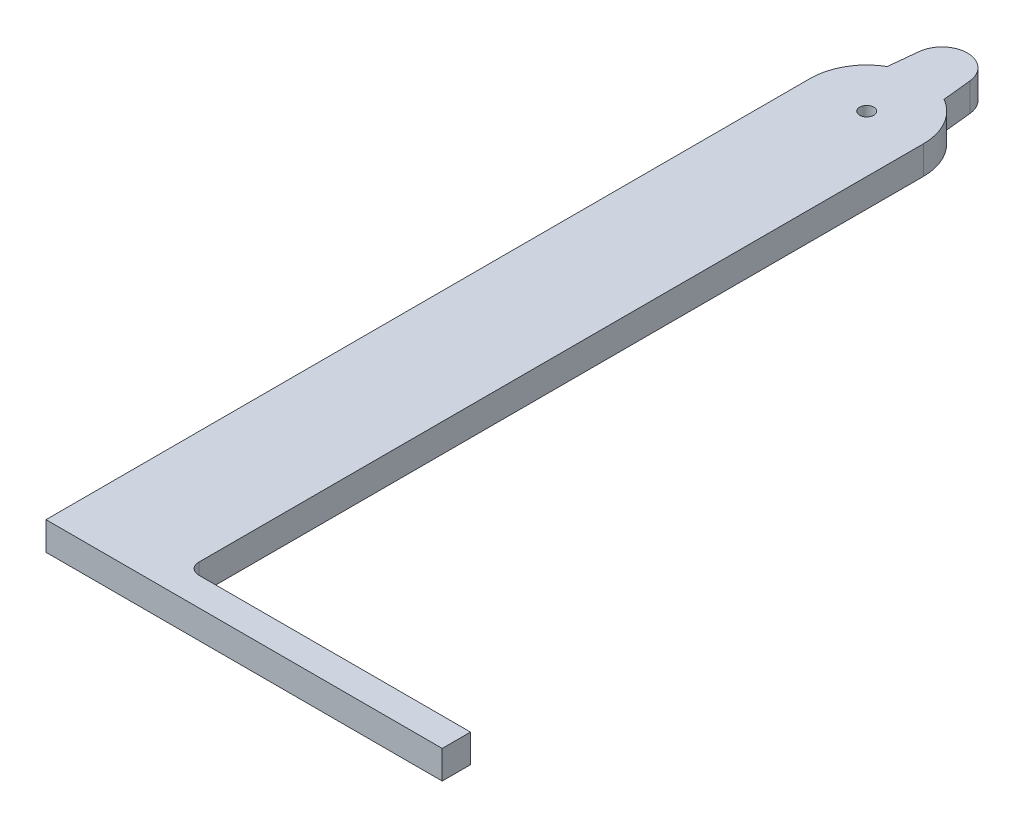
SolidWorks part; units mm, degrees
ref_plane "Front Plane" through (0, 0, 0) normal (0, 0, 1) x (1, 0, 0)
ref_plane "Top Plane" through (0, 0, 0) normal (0, 1, 0) x (1, 0, 0)
ref_plane "Right Plane" through (0, 0, 0) normal (1, 0, 0) x (0, 0, -1)
sketch "Sketch1" plane through (0, 0, 0) normal (0, 1, 0) x (1, 0, 0)
  line L1 (-12.7, 0) -> (12.7, 0)
  line L2 (-12.7, 0) -> (-12.7, -165.1)
  line L3 (-12.7, -165.1) -> (12.7, -165.1)
  line L4 (12.7, 0) -> (12.7, -165.1)
  circle A0 centre (0, 0) radius 12.7
  dimension "D1" = 25.4
  dimension "D2" = 165.1
extrude "Boss-Extrude1" add sketch "Sketch1" along normal blind 6.35 contours A0 L2 L3 L4 | L1 A0 | L1 A0 region at (0, 0, -5.39) region at (0, 0, 87.5114) region at (0, 0, 5.39)
sketch "Sketch2" plane through (0, 6.35, 0) normal (0, 1, 0) x (1, 0, 0)
  line L1 (-12.7, -165.1) -> (76.2, -165.1)
  line L2 (-12.7, -165.1) -> (-12.7, -171.45)
  line L3 (-12.7, -171.45) -> (76.2, -171.45)
  line L4 (76.2, -165.1) -> (76.2, -171.45)
  dimension "D1" = 88.9
  dimension "D2" = 6.35
extrude "Boss-Extrude2" add sketch "Sketch2" against normal up to surface (6.35 mm away) up to face at (0, 0, 79.375)
fillet "Fillet1" radius 2.54 1 edges
sketch "Sketch3" plane through (0, 0, 0) normal (0, -1, 0) x (-1, 0, 0)
  line L4 (-7.3841, 1.2138) -> (7.3841, 1.2138)
  line L6 (-7.3841, 1.2138) -> (-5.6981, 17.4684)
  line L7 (5.6981, 17.4684) -> (7.3841, 1.2138)
  line L8 (-7.3841, 1.2138) -> (-5.6981, 17.4684)
  line L9 (5.6981, 17.4684) -> (7.3841, 1.2138)
  arc A3 (5.6981, 17.4684) -> (-5.6981, 17.4684) centre (0, 16.8774) ccw
  arc A4 (5.6981, 17.4684) -> (-5.6981, 17.4684) centre (0, 16.8774) ccw
  dimension "D1" = 3.175
extrude "Boss-Extrude3" add sketch "Sketch3" against normal up to surface (6.35 mm away) up to face at (28.2277, 6.35, 106.0294)
sketch "Sketch4" plane through (0, 6.35, 0) normal (0, 1, 0) x (1, 0, 0)
  circle A0 centre (0, 0) radius 1.5875
  dimension "D1" = 3.175
extrude "Cut-Extrude1" cut sketch "Sketch4" against normal through all
